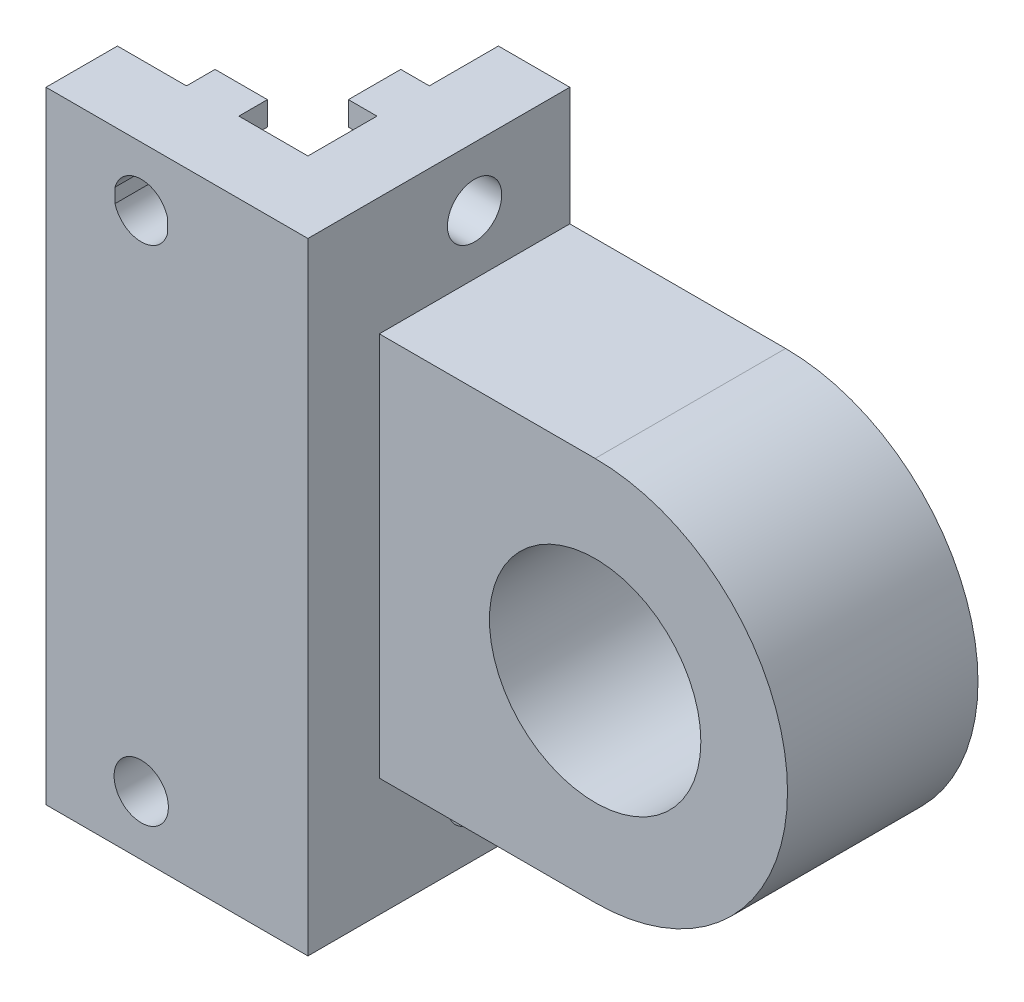
SolidWorks part; units mm, degrees
note: The reader was unsure of these and kept them because the rebuilt part matched: shared geometry of "Эскиз19<14>".
ref_plane "Спереди" through (0, 0, 0) normal (0, 0, 1) x (1, 0, 0)
ref_plane "Сверху" through (0, 0, 0) normal (0, 1, 0) x (1, 0, 0)
ref_plane "Справа" through (0, 0, 0) normal (1, 0, 0) x (0, 0, -1)
sketch "Эскиз2" plane through (0, 0, 0) normal (0, 0, 1) x (1, 0, 0)
  line L0 (-20.1596, 0) -> (-30.1596, 0)
  line L1 (0, 20.2) -> (-22.6596, 20.2)
  line L3 (0, -20.2) -> (-22.6596, -20.2)
  line L5 (15.0785, 13.4417) -> (-22.6596, -20.2) construction
  line L6 (15.0785, -13.4417) -> (-22.6596, 20.2) construction
  line L7 (-22.6596, -20.2) -> (-22.6596, -32.6234)
  line L8 (-22.6596, -32.6234) -> (-30.1596, -32.6234)
  line L9 (-30.1596, -32.6234) -> (-30.1596, 32.6234)
  line L10 (-22.6596, 20.2) -> (-22.6596, 32.6234)
  line L11 (-22.6596, 32.6234) -> (-30.1596, 32.6234)
  circle A0 centre (0, 0) radius 11.1
  arc A1 (0, -20.2) -> (0, 20.2) centre (0, 0) ccw
  dimension "D1" = 22.2
  dimension "D2" = 40.4
  dimension "D3" = 40.4
  dimension "D4" = 10
extrude "Бобышка-Вытянуть4" add sketch "Эскиз2" along normal blind 20
sketch "Эскиз8" plane through (-22.6596, 0, 0) normal (1, 0, 0) x (0, 0, -1)
  line L0 (-10, 32.6234) -> (-10, 20.2)
  line L1 (-20, 32.6234) -> (0, 32.6234) construction
  line L2 (-20, 20.2) -> (0, 20.2) construction
  line L3 (-10, -32.6234) -> (-10, -20.2)
  line L4 (-20, -32.6234) -> (0, -32.6234) construction
  line L5 (-20, -20.2) -> (0, -20.2) construction
  circle A0 centre (-10, 26.4117) radius 2.85
  circle A1 centre (-10, -26.4117) radius 2.85
extrude "Вырез-Вытянуть1" cut sketch "Эскиз8" against normal blind 10 contours L3 A1 | L3 A1 | L0 A0 | L0 A0
sketch "Эскиз9" plane through (-30.1596, 0, 0) normal (-1, 0, 0) x (0, 0, 1)
  line L0 (0, -32.6234) -> (20, -32.6234)
  line L1 (10, -32.6234) -> (10, 32.6234)
  line L2 (20, 32.6234) -> (0, 32.6234) construction
sketch "Эскиз11" plane through (-30.1596, 0, 0) normal (-1, 0, 0) x (0, 0, 1)
  point P0 (4.989, -29.9134)
  dimension "D1" = 2.71
sketch "Эскиз14" plane through (-22.6596, 0, 0) normal (1, 0, 0) x (0, 0, -1)
  line L0 (-20, -32.6234) -> (0, -32.6234)
  point P4 (-10, -26.4117)
  dimension "D1" = 6.2117
sketch "Эскиз15" plane through (-30.1596, 0, 0) normal (-1, 0, 0) x (0, 0, 1)
  line L0 (7.756, -30.1217) -> (0, -30.1217)
  line L1 (0, -32.6234) -> (0, 32.6234) construction
  line L2 (0, -30.1217) -> (0, -32.6234)
  line L3 (0, -32.6234) -> (20, -32.6234)
  line L4 (20, -32.6234) -> (20, -30.1217)
  line L5 (20, -32.6234) -> (20, 32.6234) construction
  line L6 (20, -30.1217) -> (7.756, -30.1217)
  line L7 (7.25, -32.6234) -> (7.25, -30.1217)
  line L8 (7.25, -30.1217) -> (6.6273, -30.1217)
  line L10 (6.6273, -32.6234) -> (7.25, -32.6234)
  line L11 (7.25, -32.6234) -> (7.25, -30.1217)
  line L12 (20, 32.6234) -> (0, 32.6234) construction
  line L14 (12.75, 32.6234) -> (12.75, 30.1217)
  line L15 (7.25, 32.6234) -> (7.25, 30.1217)
  line L18 (12.75, 30.1217) -> (7.25, 30.1217)
  line L19 (7.25, 32.6234) -> (12.75, 32.6234)
  line L20 (12.75, 32.6234) -> (12.75, 30.1217)
  line L21 (10, 30.1217) -> (10, 22.7017)
  line L22 (10, 22.7017) -> (12.75, 22.7017)
  line L23 (12.75, 22.7017) -> (12.75, -22.7017)
  line L24 (12.75, -22.7017) -> (7.25, -22.7017)
  line L25 (7.25, -22.7017) -> (7.25, 22.7017)
  line L26 (7.25, 22.7017) -> (10, 22.7017)
  line L27 (10, -22.7017) -> (10, -30.1217)
  line L28 (7.25, -32.6234) -> (12.75, -32.6234)
  line L29 (7.25, 30.1217) -> (7.25, 32.6234)
  line L30 (12.75, 22.7017) -> (12.75, -22.7017)
  line L31 (12.75, -30.1217) -> (12.75, -32.6234)
  line L32 (7.25, -22.7017) -> (7.25, 22.7017)
  line L33 (7.25, -22.7017) -> (7.25, -30.1217)
  line L34 (12.75, -22.7017) -> (12.75, -30.1217)
  line L35 (12.75, 30.1217) -> (12.75, 22.7017)
  line L36 (7.25, 30.1217) -> (7.25, 22.7017)
  point P0 (10, -32.6234)
  point P1 (7.756, -30.1217)
  point P7 (7.25, -32.6234)
  point P16 (12.75, -32.6234)
  point P23 (7.25, 30.1217)
  point P24 (0, 32.6234)
  point P25 (12.75, 32.6234)
  point P37 (10, -26.4117)
  point P38 (10, -22.7017)
  point P40 (10, 26.4117)
  point P41 (10, 22.7017)
  line M6 (20, 32.6234) -> (0, 32.6234)
  dimension "D9" = 2.5017
  dimension "D1" = 3.71
  dimension "D2" = 7.25
  dimension "D3" = 5.5
  dimension "D4" = 3.71
  dimension "D5" = 7.25
  dimension "D6" = 5.5
  dimension "D7" = 3.71
  dimension "D8" = 3.71
sketch "Эскиз17" plane through (-30.1596, 0, 0) normal (-1, 0, 0) x (0, 0, 1)
  line L0 (7.25, 32.6234) -> (12.75, 32.6234)
extrude "Бобышка-Вытянуть5" add sketch "Эскиз15" along normal blind 3 contours L26 L25 L24 L23 L22 | L18 L14 L15 M6 | L31 L6 L0 L7 L3
sketch "Эскиз18" plane through (0, 0, 20) normal (0, 0, 1) x (1, 0, 0)
  line L0 (-30.1596, -32.6234) -> (-50.1596, -32.6234)
  line L1 (-50.1596, -32.6234) -> (-50.1596, 32.6234)
  line L2 (-50.1596, 32.6234) -> (-30.1596, 32.6234)
  line L3 (-30.1596, -32.6234) -> (-22.6596, -32.6234)
  line L4 (-22.6596, -32.6234) -> (-22.6596, 32.6234)
  line L5 (-22.6596, 32.6234) -> (-30.1596, 32.6234)
  dimension "D1" = 20
extrude "Бобышка-Вытянуть6" add sketch "Эскиз18" along normal blind 7.5
sketch "Эскиз19" plane through (0, 0, 20) normal (0, 0, -1) x (-1, 0, 0)
  line L0 (40.1596, -30.1234) -> (40.1596, -22.7034)
  line L1 (50.1596, -32.6234) -> (30.1596, -32.6234) construction
  line L2 (30.1596, 32.6234) -> (50.1596, 32.6234) construction
  line L3 (40.1596, 22.7034) -> (40.1596, 30.1234)
  line L4 (37.4096, -32.6234) -> (42.9096, -32.6234)
  line L5 (37.4096, 32.6234) -> (37.4096, -32.6234)
  line L6 (30.1596, -32.6234) -> (30.1596, -30.1217) construction
  line L7 (42.9096, 32.6234) -> (42.9096, -32.6234)
  line L8 (50.1596, 32.6234) -> (50.1596, -32.6234) construction
  line L9 (37.4096, -30.1234) -> (42.9096, -30.1234)
  line L10 (37.4096, -22.7034) -> (42.9096, -22.7034)
  line L11 (37.4096, 30.1234) -> (42.9096, 30.1234)
  line L12 (37.4096, 22.7034) -> (42.9096, 22.7034)
  line L13 (37.4096, 32.6234) -> (42.9096, 32.6234)
  circle A0 centre (40.1596, -26.4134) radius 2.85
  circle A1 centre (40.1596, 26.4134) radius 2.85
  point P6 (40.1596, -26.4134)
  point P7 (40.1596, 26.4134)
  line M2 (30.1596, -32.6234) -> (50.1596, -32.6234)
  line M4 (50.1596, 32.6234) -> (30.1596, 32.6234)
  dimension "D2" = 6.21
  dimension "D3" = 7.25
  dimension "D1" = 6.21
  dimension "D4" = 7.25
  dimension "D5" = 2.5
  dimension "D6" = 3.71
  dimension "D7" = 2.5
  dimension "D8" = 3.71
extrude "Вырез-Вытянуть2" cut sketch "Эскиз19" against normal blind 10 contours L0 A1 | L0 A1 | L0 A0
extrude "Бобышка-Вытянуть7" add sketch "Эскиз19<14>" along normal blind 3 contours L12 L5 L10 L7 | L5 L11 L7 M4 | L9 L5 L7 M2
sketch "Эскиз19<14>" plane through (0, 0, 20) normal (0, 0, -1) x (-1, 0, 0) same geometry as "Эскиз19"
